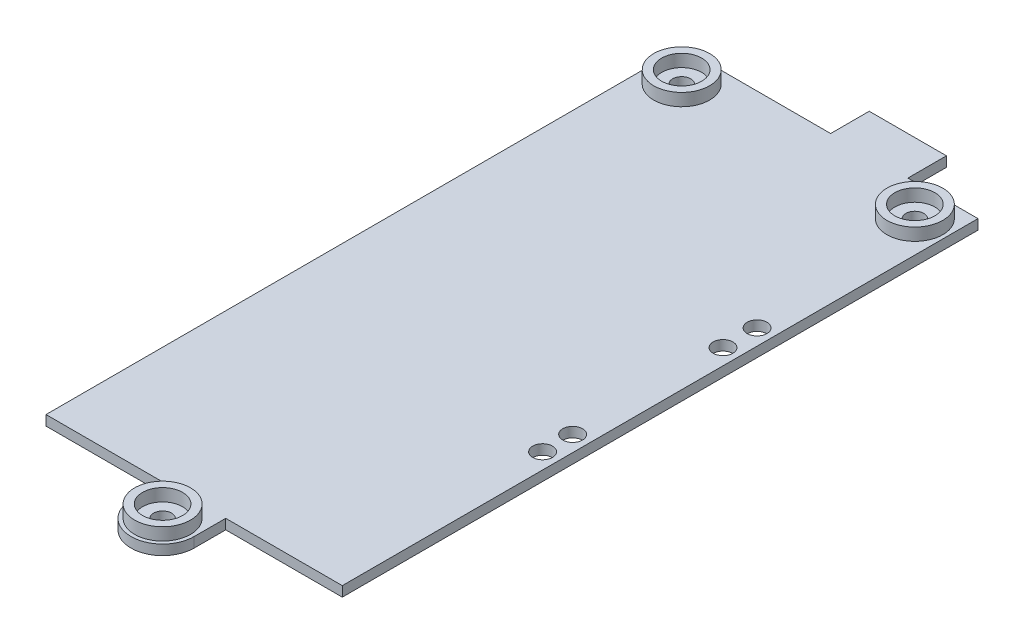
SolidWorks part; units mm, degrees
ref_plane "Front Plane" through (0, 0, 0) normal (0, 0, 1) x (1, 0, 0)
ref_plane "Top Plane" through (0, 0, 0) normal (0, 1, 0) x (1, 0, 0)
ref_plane "Right Plane" through (0, 0, 0) normal (1, 0, 0) x (0, 0, -1)
sketch "Sketch2" plane through (0, 0, 0) normal (0, 0, 1) x (1, 0, 0)
  line L0 (-30.2154, 3.088) -> (-30.2154, -12.912)
  line L1 (-30.2154, -12.912) -> (4.7846, -12.912)
  line L2 (4.7846, -12.912) -> (4.7846, 3.088)
  line L3 (-31.4854, 3.088) -> (-31.4854, -14.182)
  line L4 (-31.4854, -14.182) -> (6.0546, -14.182)
  line L5 (6.0546, -14.182) -> (6.0546, 3.088)
  line L6 (-31.4854, 3.088) -> (-30.2154, 3.088)
  line L7 (4.7846, 3.088) -> (6.0546, 3.088)
  dimension "D1" = 16
  dimension "D2" = 16
  dimension "D3" = 35
  dimension "D4" = 1.27
extrude "Boss-Extrude1" add sketch "Sketch2" along normal blind 77
sketch "Sketch3" plane through (0, 0, 77) normal (0, 0, 1) x (1, 0, 0)
  line L1 (-31.4854, 3.088) -> (6.0546, 3.088)
  line L2 (-31.4854, 3.088) -> (-31.4854, -14.182)
  line L3 (-31.4854, -14.182) -> (6.0546, -14.182)
  line L4 (6.0546, 3.088) -> (6.0546, -14.182)
extrude "Boss-Extrude2" add sketch "Sketch3" along normal blind 1.77
sketch "Sketch4" plane through (0, 0, 0) normal (0, 0, -1) x (-1, 0, 0)
  line L1 (-6.0546, 3.088) -> (31.4854, 3.088)
  line L2 (-6.0546, 3.088) -> (-6.0546, -14.182)
  line L3 (-6.0546, -14.182) -> (31.4854, -14.182)
  line L4 (31.4854, 3.088) -> (31.4854, -14.182)
extrude "Boss-Extrude3" add sketch "Sketch4" along normal blind 1.77
sketch "Sketch5" plane through (0, 0, -1.77) normal (0, 0, -1) x (-1, 0, 0)
  line L0 (31.4854, 3.088) -> (-6.0546, 3.088) construction
  line L1 (17.2154, 3.088) -> (21.2154, 3.088)
  line L2 (17.2154, 3.088) -> (17.2154, -12.912)
  line L3 (17.2154, -12.912) -> (21.2154, -12.912)
  line L4 (21.2154, 3.088) -> (21.2154, -12.912)
  line L5 (-4.7846, -12.912) -> (30.2154, -12.912) construction
  line L6 (30.2154, -12.912) -> (30.2154, 3.088) construction
  dimension "D1" = 4
  dimension "D2" = 9
extrude "Cut-Extrude2" cut sketch "Sketch5" against normal blind 1.77
sketch "Sketch6" plane through (0, 3.088, 0) normal (0, 1, 0) x (1, 0, 0)
  line L0 (4.7846, -77) -> (4.7846, 0) construction
  line L1 (-11.3454, 5.39) -> (-4.1054, 5.39)
  line L2 (-11.3454, 5.39) -> (-11.3454, -1.85)
  line L3 (-11.3454, -1.85) -> (-4.1054, -1.85)
  line L4 (-4.1054, 5.39) -> (-4.1054, -1.85)
  line L5 (-12.6154, 6.66) -> (-2.8354, 6.66)
  line L6 (-12.6154, 6.66) -> (-12.6154, -4.39)
  line L7 (-12.6154, -4.39) -> (-2.8354, -4.39)
  line L8 (-2.8354, 6.66) -> (-2.8354, -4.39)
  line L9 (-17.2154, 1.77) -> (6.0546, 1.77) construction
  dimension "D1" = 1.27
  dimension "D2" = 1.27
  dimension "D3" = 8.89
  dimension "D4" = 7.24
  dimension "D5" = 1.27
  dimension "D6" = 2.54
  dimension "D7" = 7.24
  dimension "D8" = 3.62
extrude "button_walls" add sketch "Sketch6" against normal blind 7.24
sketch "Sketch7" plane through (0, -4.152, 0) normal (0, -1, 0) x (1, 0, 0)
  line L1 (-12.6154, 4.39) -> (-2.8354, 4.39)
  line L2 (-12.6154, 4.39) -> (-12.6154, -6.66)
  line L3 (-12.6154, -6.66) -> (-2.8354, -6.66)
  line L4 (-2.8354, 4.39) -> (-2.8354, -6.66)
extrude "button_bottom" add sketch "Sketch7" along normal blind 1.27
sketch "Sketch8" plane through (0, 3.088, 0) normal (0, 1, 0) x (1, 0, 0)
  line L0 (-11.3454, 0) -> (-4.1054, 0) construction
  line L1 (-11.3454, 1.77) -> (-4.1054, 1.77)
  line L2 (-11.3454, 1.77) -> (-11.3454, 0)
  line L3 (-11.3454, 0) -> (-4.1054, 0)
  line L4 (-4.1054, 1.77) -> (-4.1054, 0)
extrude "button_cutout_middle" cut sketch "Sketch8" against normal blind 7.24
sketch "Sketch9" plane through (0, 3.088, 0) normal (0, 1, 0) x (1, 0, 0)
  line L0 (-7.7254, 9.378) -> (-7.7254, -7.9569) construction
  line L1 (-2.8354, 6.66) -> (-12.6154, 6.66) construction
  line L2 (-9.9454, 6.66) -> (-5.4954, 6.66)
  line L3 (-9.9454, 6.66) -> (-9.9454, 5.39)
  line L4 (-9.9454, 5.39) -> (-5.4954, 5.39)
  line L5 (-5.4954, 6.66) -> (-5.4954, 5.39)
  line L6 (-4.1054, 5.39) -> (-11.3454, 5.39) construction
  line L13 (-12.6154, -4.39) -> (-2.8354, -4.39) construction
  line L14 (-12.6154, 0) -> (-9.2454, 0)
  line L15 (-12.6154, 0) -> (-12.6154, -4.39)
  line L16 (-12.6154, -4.39) -> (-9.2454, -4.39)
  line L17 (-9.2454, 0) -> (-9.2454, -4.39)
  line L19 (-2.8354, 0) -> (-6.2054, 0)
  line L20 (-2.8354, 0) -> (-2.8354, -4.39)
  line L21 (-2.8354, -4.39) -> (-6.2054, -4.39)
  line L22 (-6.2054, 0) -> (-6.2054, -4.39)
  dimension "D1" = 4.45
  dimension "D2" = 2.22
  dimension "D3" = 1.52
  dimension "D4" = 1.52
extrude "button_cutout_front_back" cut sketch "Sketch9" against normal blind 7.24
sketch "Sketch10" plane through (0, -4.152, 0) normal (0, 1, 0) x (1, 0, 0)
  line L1 (-12.6154, 0) -> (-9.2454, 0)
  line L2 (-12.6154, 0) -> (-12.6154, -4.39)
  line L3 (-12.6154, -4.39) -> (-9.2454, -4.39)
  line L4 (-9.2454, 0) -> (-9.2454, -4.39)
  line L5 (-2.8354, 0) -> (-6.2054, 0)
  line L6 (-2.8354, 0) -> (-2.8354, -4.39)
  line L7 (-2.8354, -4.39) -> (-6.2054, -4.39)
  line L8 (-6.2054, 0) -> (-6.2054, -4.39)
extrude "button_cutout_bottom" cut sketch "Sketch10" against normal blind 1.27
chamfer "button_Chamfer1" distance 5 angle 45 1 edges at (-7.7254, -5.422, 0)
sketch "Sketch12" plane through (0, -12.912, 0) normal (0, 1, 0) x (1, 0, 0)
  line L0 (4.7846, -77) -> (-30.2154, -77) construction
  line L1 (-30.2154, -77) -> (4.7846, -77)
  line L2 (-30.2154, -77) -> (-30.2154, -75.23)
  line L3 (-30.2154, -75.23) -> (4.7846, -75.23)
  line L4 (4.7846, -77) -> (4.7846, -75.23)
  line L5 (4.7846, -77) -> (4.7846, 0) construction
  line L11 (4.7846, -77) -> (4.7846, 0) construction
  line L12 (-27.9854, -55.23) -> (-26.2154, -55.23)
  line L13 (-27.9854, -55.23) -> (-27.9854, -65.23)
  line L14 (-27.9854, -65.23) -> (-26.2154, -65.23)
  line L15 (-26.2154, -55.23) -> (-26.2154, -65.23)
  line L16 (4.7846, -37.73) -> (-60.4587, -37.73) construction
  line L17 (-2.7154, -35.96) -> (4.7846, -35.96)
  line L18 (-2.7154, -35.96) -> (-2.7154, -37.73)
  line L19 (-2.7154, -37.73) -> (4.7846, -37.73)
  line L20 (4.7846, -35.96) -> (4.7846, -37.73)
  line L21 (-25.7839, -37.73) -> (-19.7648, -37.73)
  line L22 (-54.4351, -21.6) -> (25.4799, -21.6) construction
  line L24 (-12.9854, -19.83) -> (-11.2154, -19.83)
  line L25 (-12.9854, -19.83) -> (-12.9854, -26.83)
  line L26 (-12.9854, -26.83) -> (-11.2154, -26.83)
  line L27 (-11.2154, -19.83) -> (-11.2154, -26.83)
  arc A0 (-19.7648, -37.73) -> (-25.7839, -37.73) centre (-22.7744, -34.8868) ccw
  circle A1 centre (-22.7744, -34.8868) radius 0.9652
  point P29 (-12.1004, -19.83)
  dimension "D11" = 8.2804
  dimension "D12" = 1.9304
  dimension "D1" = 1.77
  dimension "D2" = 31
  dimension "D3" = 1.77
  dimension "D4" = 10
  dimension "D5" = 10
  dimension "D6" = 1.77
  dimension "D7" = 7.5
  dimension "D8" = 37.5
  dimension "D9" = 42.1132
  dimension "D10" = 27.559
  dimension "D13" = 55.4
  dimension "D14" = 1.77
  dimension "D15" = 7
  dimension "D16" = 1.77
  dimension "D17" = 16
extrude "support_pcb_battery" add sketch "Sketch12" along normal blind 7
sketch "Sketch13" plane through (6.0546, 0, 0) normal (1, 0, 0) x (0, 0, -1)
  line L0 (-77, 3.088) -> (-77, -22.3902) construction
  line L1 (-81.5091, -5.912) -> (21.2567, -5.912) construction
  line L3 (-39.2868, -1.012) -> (-30.4868, -1.012)
  line L4 (-39.2868, -1.012) -> (-39.2868, -5.812)
  line L5 (-39.2868, -5.812) -> (-30.4868, -5.812)
  line L6 (-30.4868, -1.012) -> (-30.4868, -5.812)
  circle A0 centre (-51.3968, -3.412) radius 1.25
  circle A1 centre (-47.5868, -3.412) radius 1.25
  circle A2 centre (-24.2188, -3.412) radius 1.25
  point P10 (-30.4868, -3.412)
  point P11 (-34.8868, -1.012)
  dimension "D7" = 2.5
  dimension "D8" = 2.5
  dimension "D11" = 2.5
  dimension "D1" = 8.8
  dimension "D2" = 2.5
  dimension "D3" = 4.8
  dimension "D4" = 42.1132
  dimension "D5" = 2.5
  dimension "D6" = 2.5
  dimension "D9" = 25.6032
  dimension "D10" = 29.4132
  dimension "D12" = 2.5
  dimension "D13" = 52.7812
extrude "cutout_usb_3_leds" cut sketch "Sketch13" against normal blind 1.77
sketch "Sketch16" plane through (0, -5.912, 0) normal (0, 1, 0) x (1, 0, 0)
  line L0 (-11.2154, -26.83) -> (-11.2154, -19.83) construction
  line L1 (-12.9854, -19.83) -> (-11.2154, -19.83)
  line L2 (-12.9854, -19.83) -> (-12.9854, -21.6)
  line L3 (-12.9854, -21.6) -> (-11.2154, -21.6)
  line L4 (-11.2154, -19.83) -> (-11.2154, -21.6)
  dimension "D1" = 1.77
extrude "tab_pcb_retainer_len" add sketch "Sketch16" along normal blind 3
sketch "Sketch17" plane through (0, 3.088, 0) normal (0, 1, 0) x (1, 0, 0)
  line L0 (4.7846, -77) -> (-30.2154, -77) construction
  line L1 (-22.3614, -77) -> (-18.3614, -77)
  line L2 (-22.3614, -77) -> (-22.3614, -78.77)
  line L3 (-22.3614, -78.77) -> (-18.3614, -78.77)
  line L4 (-18.3614, -77) -> (-18.3614, -78.77)
  line L5 (6.0546, -78.77) -> (-31.4854, -78.77) construction
  line L7 (4.7846, -77) -> (4.7846, 0) construction
  point P8 (-20.3614, -77)
  dimension "D1" = 25.146
  dimension "D2" = 4
extrude "cutout_back_mot_wires" cut sketch "Sketch17" against normal up to surface (9 mm away) up to face at (-12.7154, -5.912, 76.115)
sketch "Sketch18" plane through (6.0546, 0, 0) normal (1, 0, 0) x (0, 0, -1)
  line L0 (-77, 3.088) -> (-77, -25.415) construction
  line L1 (-78.77, -5.912) -> (19.6061, -5.912) construction
  circle A0 centre (-28.5368, -3.412) radius 1.25
  dimension "D1" = 2.5
  dimension "D2" = 2.5
  dimension "D3" = 48.4632
extrude "cutout_chg_done_led" cut sketch "Sketch18" against normal blind 10
sketch "Sketch19" plane through (0, -12.912, 0) normal (0, 1, 0) x (1, 0, 0)
  line L0 (-30.2154, -77) -> (38.3127, -77) construction
  line L1 (4.7846, 0) -> (4.7846, -88.7648) construction
  line L2 (-26.0154, 10.814) -> (-26.0154, -88.7648) construction
  line L3 (-30.2154, -77) -> (-30.2154, 0) construction
  line L4 (-30.2154, -67.73) -> (-26.0154, -67.73)
  line L5 (-30.2154, -67.73) -> (-30.2154, -69.5)
  line L6 (-30.2154, -69.5) -> (-26.0154, -69.5)
  line L7 (-26.0154, -67.73) -> (-26.0154, -69.5)
  line L9 (-30.2154, -45.23) -> (-26.0154, -45.23)
  line L10 (-30.2154, -45.23) -> (-30.2154, -47)
  line L11 (-30.2154, -47) -> (-26.0154, -47)
  line L12 (-26.0154, -45.23) -> (-26.0154, -47)
  line L13 (-30.2154, -27.23) -> (-26.0154, -27.23)
  line L14 (-30.2154, -27.23) -> (-30.2154, -29)
  line L15 (-30.2154, -29) -> (-26.0154, -29)
  line L16 (-26.0154, -27.23) -> (-26.0154, -29)
  dimension "D1" = 30.8
  dimension "D2" = 1.77
  dimension "D3" = 7.5
  dimension "D4" = 1.77
  dimension "D5" = 30
  dimension "D6" = 1.77
  dimension "D7" = 48
extrude "tab_pcb_retainers_width" add sketch "Sketch19" along normal blind 10
sketch "Sketch20" plane through (0, 0, 69.5) normal (0, 0, 1) x (1, 0, 0)
  line L0 (-26.0154, -2.912) -> (-33.8352, -2.912) construction
  line L1 (-26.0154, -5.912) -> (-34.7157, -5.912) construction
  line L2 (-30.2154, -5.912) -> (-22.3614, -5.912) construction
  line L3 (-26.0154, -2.912) -> (-26.0154, -12.912) construction
  line L4 (-28.4454, -0.8533) -> (-28.4454, -17.345) construction
  line L5 (-30.2154, -5.912) -> (-30.2154, 3.088) construction
  line L9 (-26.0154, -12.912) -> (-26.0154, -5.912)
  line L15 (-26.0154, -5.912) -> (-28.4454, -10.1209)
  line L16 (-28.4454, -10.1209) -> (-28.4454, -12.912)
  line L17 (-28.4454, -12.912) -> (-26.0154, -12.912)
  dimension "D1" = 1.77
  dimension "D2" = 30
extrude "cutout_retainer_tab_1" cut sketch "Sketch20" against normal blind 1.77
sketch "Sketch21" plane through (0, 0, 47) normal (0, 0, 1) x (1, 0, 0)
  line L0 (-26.0154, -5.912) -> (-28.4454, -10.1209)
  line L1 (-28.4454, -10.1209) -> (-28.4454, -12.912)
  line L2 (-28.4454, -12.912) -> (-26.0154, -12.912)
  line L3 (-26.0154, -12.912) -> (-26.0154, -5.912)
extrude "cutout_retainer_tab_2" cut sketch "Sketch21" against normal blind 1.77
sketch "Sketch23" plane through (0, -14.182, 0) normal (0, -1, 0) x (1, 0, 0)
  line L0 (-12.7154, 88.9305) -> (-12.7154, -20.1968) construction
  line L1 (-37.0904, 86.77) -> (37.2604, 86.77) construction
  line L2 (-31.4854, 78.77) -> (6.0546, 78.77) construction
  line L3 (-37.0904, 82.77) -> (5.1204, 82.77) construction
  line L8 (6.0546, -1.77) -> (-1.9454, -1.77)
  line L9 (6.0546, -1.77) -> (6.0546, 6.23)
  line L10 (6.0546, 6.23) -> (-1.9454, 6.23)
  line L11 (-1.9454, -1.77) -> (-1.9454, 6.23)
  line L12 (-31.4854, -1.77) -> (-23.4854, -1.77)
  line L13 (-31.4854, -1.77) -> (-31.4854, 6.23)
  line L14 (-31.4854, 6.23) -> (-23.4854, 6.23)
  line L15 (-23.4854, -1.77) -> (-23.4854, 6.23)
  line L16 (-8.7154, 86.77) -> (-8.7154, 78.4197) construction
  line L18 (-16.7154, 88.4048) -> (-16.7154, 77.7225) construction
  line L20 (-16.7154, 82.77) -> (-16.7154, 78.77)
  line L21 (-16.7154, 78.77) -> (-8.7154, 78.77)
  line L22 (-8.7154, 78.77) -> (-8.7154, 82.77)
  arc A0 (-16.7154, 82.77) -> (-8.7154, 82.77) centre (-12.7154, 82.77) cw
  circle A2 centre (-27.4854, 2.23) radius 0.9652
  circle A3 centre (2.0546, 2.23) radius 0.9652
  circle A4 centre (-12.7154, 82.77) radius 0.9652
  point P21 (-12.7154, 82.77)
  point P23 (-12.7154, 86.77)
  point P24 (-12.7154, 86.77)
  point P25 (-16.7154, 82.77)
  point P26 (-16.7154, 78.77)
  point P31 (-8.7154, 78.77)
  point P32 (-8.7154, 82.77)
  line M18 (-31.4854, 78.77) -> (-31.4854, -1.77)
  line M19 (-31.4854, -1.77) -> (6.0546, -1.77)
  line M20 (6.0546, -1.77) -> (6.0546, 78.77)
  line M21 (6.0546, 78.77) -> (-31.4854, 78.77)
  dimension "D9" = 1.9304
  dimension "D14" = 1.9304
  dimension "D15" = 1.9304
  dimension "D1" = 8
  dimension "D2" = 8
  dimension "D3" = 8
  dimension "D4" = 8
  dimension "D5" = 8
  dimension "D6" = 4
  dimension "D7" = 4
  dimension "D8" = 4
  dimension "D10" = 4
  dimension "D11" = 4
  dimension "D12" = 4
  dimension "D13" = 4
extrude "casing_screw_posts" add sketch "Sketch23" along direction (0, -1, 0) on the side against the normal up to surface (17.27 mm away) contours A0 L20 L22 M21 | L15 L14 A2 M19 M18 | L11 L10 A3 M19 M20 region at (2.0546, -14.182, -1.6569) region at (-27.4854, -14.182, -1.6569) region at (-12.7154, -14.182, 78.8831) up to face at (-3.3264, 3.088, 23.6583)
sketch "Sketch24" plane through (0, 3.088, 0) normal (0, 1, 0) x (1, 0, 0)
  line L0 (-16.7154, -82.77) -> (-16.7154, -78.77)
  line L1 (-16.7154, -78.77) -> (-31.4854, -78.77)
  line L2 (-31.4854, -78.77) -> (-31.4854, 1.77)
  line L3 (-31.4854, 1.77) -> (-12.6154, 1.77)
  line L4 (-12.6154, 1.77) -> (-12.6154, 6.66)
  line L5 (-12.6154, 6.66) -> (-2.8354, 6.66)
  line L6 (-2.8354, 6.66) -> (-2.8354, 1.77)
  line L7 (-2.8354, 1.77) -> (6.0546, 1.77)
  line L8 (6.0546, 1.77) -> (6.0546, -78.77)
  line L9 (6.0546, -78.77) -> (-8.7154, -78.77)
  line L10 (-8.7154, -78.77) -> (-8.7154, -82.77)
  line L11 (-12.7154, -82.77) -> (-0.9717, -82.77) construction
  line L12 (-12.7154, -82.77) -> (-22.4665, -82.77) construction
  arc A0 (-8.7154, -82.77) -> (-16.7154, -82.77) centre (-12.7154, -82.77) cw
  circle A1 centre (2.0546, -2.23) radius 0.9652
  circle A2 centre (-27.4854, -2.23) radius 0.9652
  circle A3 centre (-12.7154, -82.77) radius 0.9652
  line M1 (6.0546, -78.77) -> (6.0546, 1.77)
  line M2 (6.0546, 1.77) -> (-2.8354, 1.77)
  line M3 (-2.8354, 1.77) -> (-2.8354, 6.66)
  line M4 (-2.8354, 6.66) -> (-5.4954, 6.66)
  line M5 (-5.4954, 6.66) -> (-5.4954, 5.39)
  line M6 (-5.4954, 5.39) -> (-4.1054, 5.39)
  line M7 (-4.1054, 5.39) -> (-4.1054, 0)
  line M8 (-4.1054, 0) -> (-1.9454, 0)
  line M9 (-1.9454, 0) -> (-1.9454, -6.23)
  line M10 (-1.9454, -6.23) -> (4.7846, -6.23)
  line M11 (4.7846, -6.23) -> (4.7846, -77)
  line M12 (4.7846, -77) -> (-18.3614, -77)
  line M13 (-18.3614, -77) -> (-18.3614, -78.77)
  line M14 (-18.3614, -78.77) -> (-16.7154, -78.77)
  line M15 (-16.7154, -78.77) -> (-16.7154, -82.77)
  arc M16 (-16.7154, -82.77) -> (-8.7154, -82.77) centre (-12.7154, -82.77) ccw
  line M17 (-8.7154, -82.77) -> (-8.7154, -78.77)
  line M18 (-8.7154, -78.77) -> (6.0546, -78.77)
  circle M19 centre (-12.7154, -82.77) radius 0.9652
  circle M20 centre (2.0546, -2.23) radius 0.9652
extrude "extrude_lid" add sketch "Sketch24" along normal blind 1.27 contours M18 M1 M2 M3 M4 M5 M6 M7 M8 M9 M10 M11 M12 M13 M14 M15 M16 M17 M19 M20 | L5 L4 L3 L2 L1 A2 M13 M12 M11 M10 M9 M8 M7 M6 M5 region at (-15.7497, 3.088, 80.77) region at (-13.6545, 3.088, 38.1143)
sketch "Sketch25" plane through (0, -14.182, 0) normal (0, -1, 0) x (1, 0, 0)
  line L1 (-72.8234, 119.8036) -> (45.5472, 119.8036)
  line L2 (-72.8234, 119.8036) -> (-72.8234, -41.0117)
  line L3 (-72.8234, -41.0117) -> (45.5472, -41.0117)
  line L4 (45.5472, 119.8036) -> (45.5472, -41.0117)
extrude "remove_box_material" cut sketch "Sketch25" against normal up to surface (17.27 mm away) up to face at (-7.7254, 3.088, 3.12)
sketch "Sketch26" plane through (0, 4.358, 0) normal (0, 1, 0) x (1, 0, 0)
  circle A0 centre (-27.4854, -2.23) radius 1.143
  circle A1 centre (2.0546, -2.23) radius 1.143
  circle A2 centre (-12.7154, -82.77) radius 1.143
  dimension "D1" = 2.286
  dimension "D2" = 2.286
  dimension "D3" = 2.286
extrude "thru_hole_no2_thread_96001A164" cut sketch "Sketch26" against normal blind 10
sketch "Sketch27" plane through (0, 4.358, 0) normal (0, 1, 0) x (1, 0, 0)
  circle A0 centre (-12.7154, -82.77) radius 2.54
  circle A1 centre (-12.7154, -82.77) radius 3.54
  circle A2 centre (-27.4854, -2.23) radius 2.54
  circle A3 centre (-27.4854, -2.23) radius 3.54
  circle A4 centre (2.0546, -2.23) radius 2.54
  circle A5 centre (2.0546, -2.23) radius 3.54
  dimension "D1" = 5.08
  dimension "D2" = 7.08
  dimension "D3" = 5.08
  dimension "D4" = 7.08
  dimension "D5" = 7.08
  dimension "D6" = 5.08
extrude "screw_head_recess" add sketch "Sketch27" along normal blind 1.5748
sketch "Sketch28" plane through (0, 4.358, 0) normal (0, 1, 0) x (1, 0, 0)
  line L0 (4.0546, 9.18) -> (4.0546, -92.1202) construction
  line L1 (6.0546, -78.77) -> (6.0546, 1.77) construction
  line L2 (-42.9113, -77) -> (55.412, -77) construction
  line L3 (-31.4854, -78.77) -> (-16.7154, -78.77) construction
  circle A0 centre (4.0546, -51.3968) radius 1.25
  circle A1 centre (4.0546, -47.5868) radius 1.25
  circle A2 centre (4.0546, -28.5368) radius 1.25
  circle A3 centre (4.0546, -24.2188) radius 1.25
  dimension "D7" = 2.5
  dimension "D8" = 2.5
  dimension "D9" = 2.5
  dimension "D10" = 2.5
  dimension "D1" = 2
  dimension "D2" = 1.77
  dimension "D3" = 25.6032
  dimension "D4" = 29.4132
  dimension "D5" = 48.4632
  dimension "D6" = 52.7812
extrude "cutout_leds" cut sketch "Sketch28" against normal blind 10
